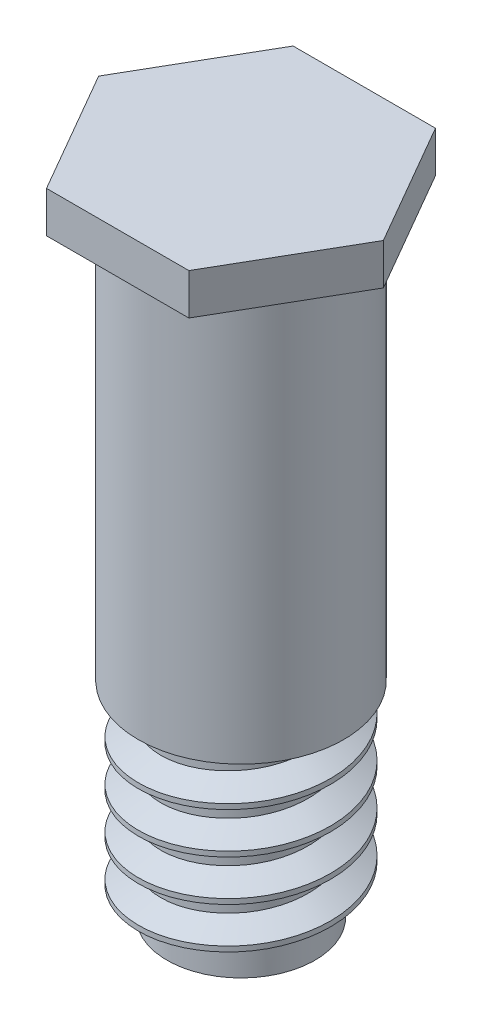
SolidWorks part; units mm, degrees
material "Alumina"
ref_plane "Front Plane" through (0, 0, 0) normal (0, 0, 1) x (1, 0, 0)
ref_plane "Top Plane" through (0, 0, 0) normal (0, 1, 0) x (1, 0, 0)
ref_plane "Right Plane" through (0, 0, 0) normal (1, 0, 0) x (0, 0, -1)
sketch "Sketch1" plane through (0, 0, 0) normal (0, 1, 0) x (1, 0, 0)
  circle A0 centre (0, 0) radius 3.175
  dimension "D1" = 6.35
extrude "Boss-Extrude1" add sketch "Sketch1" along normal blind 19.05
sketch "Sketch2" plane through (0, 19.05, 0) normal (0, 1, 0) x (1, 0, 0)
  line L1 (2.1997, -3.81) -> (4.3994, 0)
  line L2 (4.3994, 0) -> (2.1997, 3.81)
  line L3 (2.1997, 3.81) -> (-2.1997, 3.81)
  line L4 (-2.1997, 3.81) -> (-4.3994, 0)
  line L5 (-4.3994, 0) -> (-2.1997, -3.81)
  line L6 (-2.1997, -3.81) -> (2.1997, -3.81)
  circle A0 centre (0, 0) radius 3.81 construction
  dimension "D1" = 7.62
extrude "Boss-Extrude2" add sketch "Sketch2" along normal blind 1.27
sketch "Sketch6" plane through (0, 0, 0) normal (0, -1, 0) x (1, 0, 0)
  circle A0 centre (0, 0) radius 3.175
  circle A1 centre (0, 0) radius 2.286
  dimension "D1" = 6.35
  dimension "D2" = 4.572
extrude "Cut-Extrude1" cut sketch "Sketch6" against normal blind 6.35
thread "Thread3" pitch 1.27 method extrude profile "Thread Profile3" start angle 0, offset 0, length 5.334, pitch 1.27, diameter 4.572
ref_plane "Plane3" through (-2.286, 6.35, 0) normal (0, 0, 1) x (-1, 0, 0)
sketch "Thread Profile3" plane through (-2.286, 6.35, 0) normal (0, 0, 1) x (-1, 0, 0)
  line L0 (0, 0) -> (0, 1.27) construction
  line L1 (0, 0) -> (0.6874, 0.3969)
  line L2 (0.6874, 0.3969) -> (0.6874, 0.5556)
  line L3 (0.6874, 0.5556) -> (0, 0.9525)
  line L4 (0.6874, 0.4762) -> (0, 0.4762) construction
  line L11 (0, 0) -> (0, 0.9525)
  point P2 (0, 0)
  dimension "Pitch" = 1.27
  dimension "Profile_Angle" = 60
  dimension "Profile_Land" = 0.1588
  dimension "Profile_Height" = 0.6874
